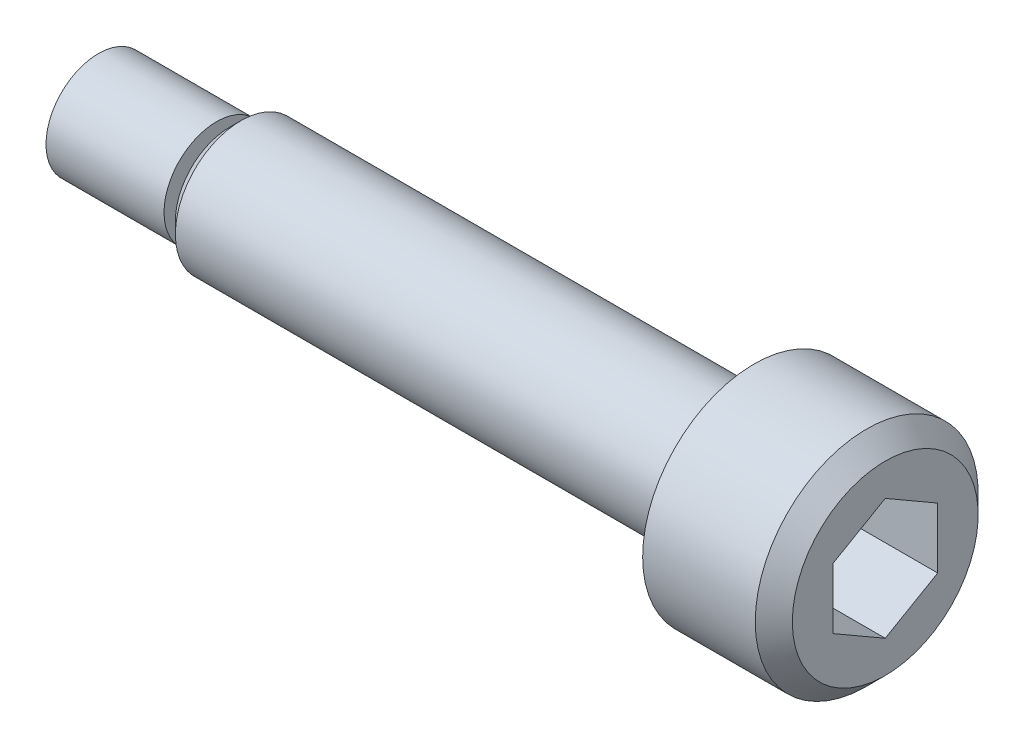
SolidWorks part; units mm, degrees
ref_plane "前视基准面" through (0, 0, 0) normal (0, 0, 1) x (1, 0, 0)
ref_plane "上视基准面" through (0, 0, 0) normal (0, 1, 0) x (1, 0, 0)
ref_plane "右视基准面" through (0, 0, 0) normal (1, 0, 0) x (0, 0, -1)
sketch "草图1" plane through (0, 0, 0) normal (0, 0, 1) x (1, 0, 0)
  line L0 (-5, 0) -> (-5, 2)
  line L1 (-5, 2) -> (-0.5, 2)
  line L2 (-0.5, 2) -> (-0.5, 1.3)
  line L3 (-0.5, 1.3) -> (0, 1.3)
  line L4 (0, 1.3) -> (0, 2.067)
  line L5 (0, 2.067) -> (0.433, 2.5)
  line L6 (0.433, 2.5) -> (20, 2.5)
  line L7 (20, 2.5) -> (20, 4.25)
  line L8 (20, 4.25) -> (24.2929, 4.25)
  line L9 (24.2929, 4.25) -> (25, 3.5429)
  line L10 (25, 3.5429) -> (25, 0)
  line L11 (25, 0) -> (-5, 0)
  line L12 (25, 0) -> (-5, 0) construction
revolve "旋转1" add sketch "草图1" angle 360 about L12 reverse direction yes
cosmetic thread "装饰螺纹线1" parameters "D1"=18.75, "D2"=4.134
sketch "草图2" plane through (0, 0, 0) normal (0, 0, 1) x (1, 0, 0)
  line L0 (19.8453, 0) -> (21, 2)
  line L1 (21, 2) -> (25, 2)
  line L2 (25, 2) -> (25, 0)
  line L3 (25, 0) -> (19.8453, 0)
  line L4 (25, 0) -> (19.8453, 0) construction
revolve "切除-旋转1" cut sketch "草图2" angle 360 about L4 reverse direction yes
ref_plane "基准面1" through (25, 0, 0) normal (1, 0, 0) x (0, 0, -1)
sketch "草图3" plane through (25, 0, 0) normal (1, 0, 0) x (0, 0, -1)
  line L0 (-2, 1.1547) -> (-2, -1.1547)
  line L1 (-2, -1.1547) -> (0, -2.3094)
  line L2 (0, -2.3094) -> (2, -1.1547)
  line L3 (2, -1.1547) -> (2, 1.1547)
  line L4 (2, 1.1547) -> (0, 2.3094)
  line L5 (0, 2.3094) -> (-2, 1.1547)
extrude "切除-拉伸1" cut sketch "草图3" against normal blind 4
ref_plane "基准面2" through (10, 0, 0) normal (1, 0, 0) x (0, 0, -1)
ref_plane "uuscbb_n XY" through (10, 0, 0) normal (1, 0, 0) x (0, 0, -1)
ref_plane "uuscbb_n XZ" through (0, 0, 0) normal (0, -1, 0) x (1, 0, 0)
ref_plane "uuscbb_n YZ" through (0, 0, 0) normal (0, 0, -1) x (-1, 0, 0)
ref_axis "uuscbb_n X" through (10, 0, 80.9) along (0, 0, -1)
ref_axis "uuscbb_n Y" through (10, -50, 0) along (0, 1, 0)
ref_axis "uuscbb_n Z" through (80.9, 0, 0) along (-1, 0, 0)
sketch3d "uuscbb_n"
  point P0 (10, 0, 0)
